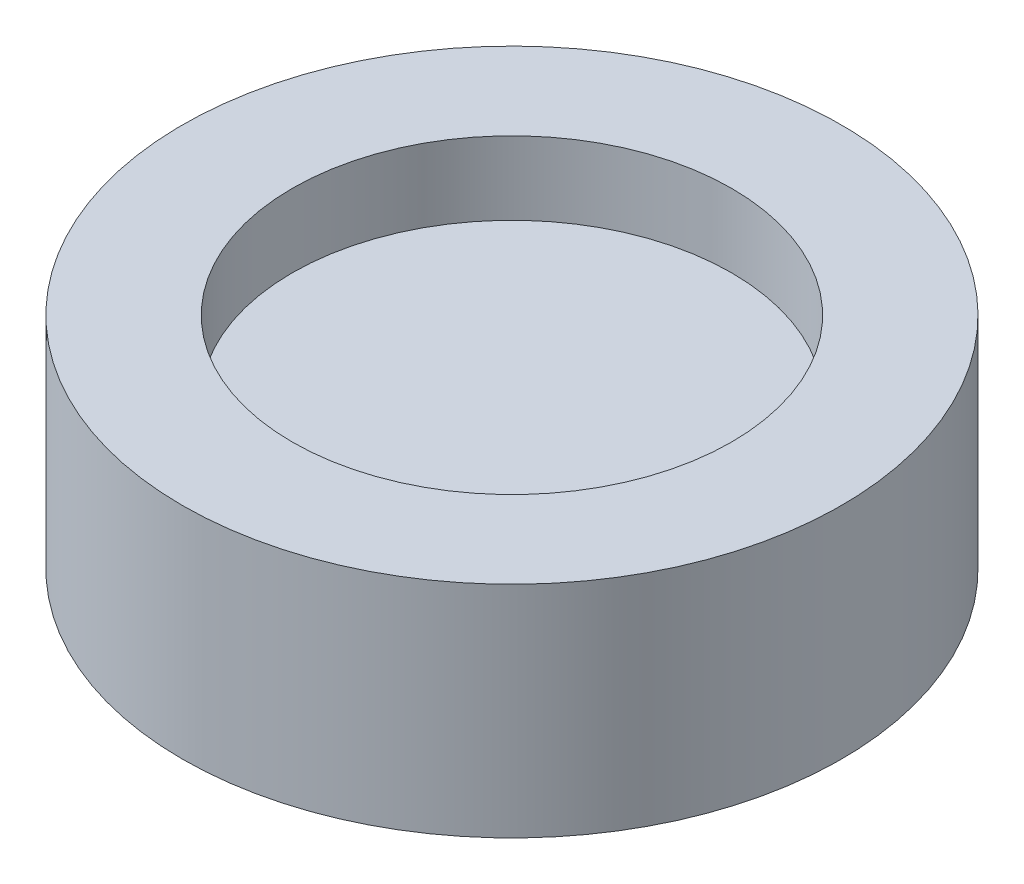
SolidWorks part; units mm, degrees
ref_plane "Front Plane" through (0, 0, 0) normal (0, 0, 1) x (1, 0, 0)
ref_plane "Top Plane" through (0, 0, 0) normal (0, 1, 0) x (1, 0, 0)
ref_plane "Right Plane" through (0, 0, 0) normal (1, 0, 0) x (0, 0, -1)
sketch "Sketch1" plane through (0, 0, 0) normal (0, 1, 0) x (1, 0, 0)
  circle A0 centre (0, 0) radius 38.1
  dimension "D1" = 76.2
extrude "Boss-Extrude1" add sketch "Sketch1" against normal blind 25.4
sketch "Sketch2" plane through (0, 0, 0) normal (0, 1, 0) x (1, 0, 0)
  circle A0 centre (0, 0) radius 25.4
  dimension "D1" = 50.8
extrude "Cut-Extrude1" cut sketch "Sketch2" against normal blind 8.4582
